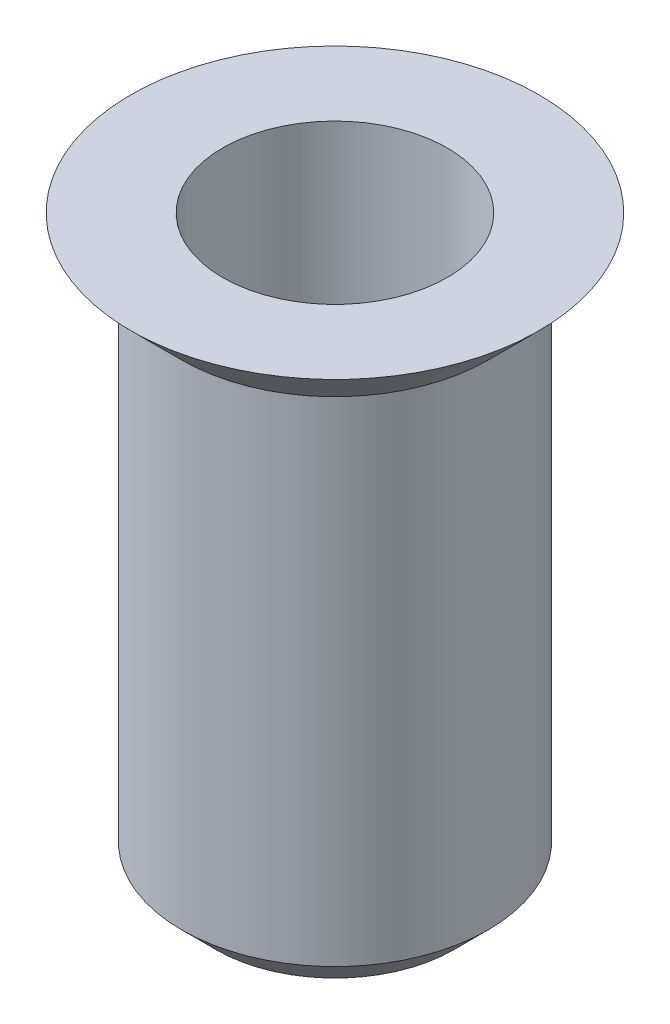
SolidWorks part; units mm, degrees
material "Handl."
ref_plane "Płaszczyzna przednia" through (0, 0, 0) normal (0, 0, 1) x (1, 0, 0)
ref_plane "Płaszczyzna górna" through (0, 0, 0) normal (0, 1, 0) x (1, 0, 0)
ref_plane "Płaszczyzna prawa" through (0, 0, 0) normal (1, 0, 0) x (0, 0, -1)
sketch "Szkic1" plane through (0, 0, 0) normal (1, 0, 0) x (0, 0, -1)
  line L0 (0, 0) -> (0, 17) construction
  line L1 (0, 0) -> (4.5, 0)
  line L2 (4.5, 0) -> (4.5, 15.5)
  line L3 (4.5, 15.5) -> (6, 17)
  line L5 (6, 17) -> (0, 17)
  line L6 (0, 0) -> (0, 17)
  dimension "D1" = 9
  dimension "D2" = 12
  dimension "D3" = 45
  dimension "D5" = 17
revolve "Obrót1" add sketch "Szkic1" angle 360 about L0
hole_wizard "Otwór pod śrubę M61" positions "Szkic2" profile "Szkic3" hole size "M6" standard "DIN"
sketch "Szkic2" plane through (0, 17, 0) normal (0, 1, 0) x (1, 0, 0)
  point P0 (0, 0)
sketch "Szkic3" plane through (0, 17, 0) normal (1, 0, 0) x (0, 0, 1)
  line L0 (0, 0) -> (0, 10.9828)
  line L1 (0, 10.9828) -> (3.3, 9)
  line L2 (3.3, 9) -> (3.3, 0)
  line L5 (3.3, 0) -> (0, 0)
  line L10 (0, 10.9828) -> (-3.3, 9) construction
  line L11 (0, -6.35) -> (0, 107.95) construction
  dimension "Średnica otworu" = 6.6
  dimension "Głębokość otworu" = 9
  dimension "Kąt wiertła" = 118
hole_wizard "Otwór gwintowany M61" positions "Szkic4" profile "Szkic5" tap size "M6" standard "DIN" end condition up to next
sketch "Szkic4" plane through (0, 17, 0) normal (0, 1, 0) x (1, 0, 0)
  point P0 (0, 0)
sketch "Szkic5" plane through (0, 17, 0) normal (1, 0, 0) x (0, 0, 1)
  line L0 (0, 0) -> (0, 17)
  line L1 (0, 17) -> (2.5, 17)
  line L2 (2.5, 17) -> (2.5, 0)
  line L5 (2.5, 0) -> (0, 0)
  line L11 (0, -6.35) -> (0, 107.95) construction
  dimension "Średnica otworu gwintowanego na wylot" = 5
  dimension "Głębokość otworu gwintowanego na wylot" = 17
cosmetic thread "Gwint otworu1"
chamfer "Sfazowanie1" distance 1 angle 45 1 edges at (0, 0, -4.5)
